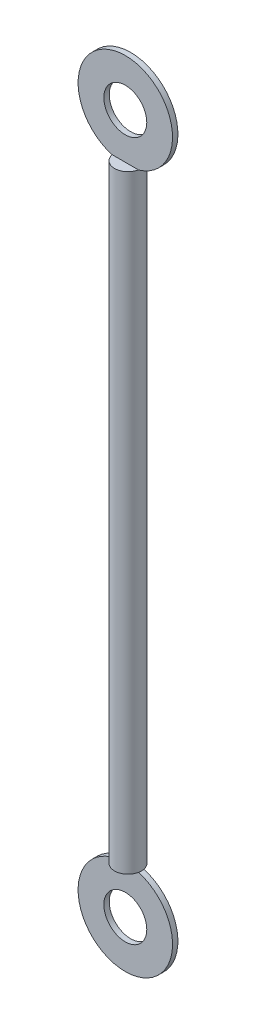
SolidWorks part; units mm, degrees
ref_plane "Front Plane" through (0, 0, 0) normal (0, 0, 1) x (1, 0, 0)
ref_plane "Top Plane" through (0, 0, 0) normal (0, 1, 0) x (1, 0, 0)
ref_plane "Right Plane" through (0, 0, 0) normal (1, 0, 0) x (0, 0, -1)
sketch "Sketch1" plane through (0, 0, 0) normal (0, 0, 1) x (1, 0, 0)
  line L0 (-7.9375, 26.7888) -> (7.9375, 26.7888) construction
  line L1 (0, 386.813) -> (0, 26.7888)
  line L2 (-7.9375, 26.7888) -> (7.9375, 26.7888)
  line L3 (-7.9375, 26.7888) -> (-7.9375, 386.813)
  line L4 (-7.9375, 386.813) -> (7.9375, 386.813)
  line L5 (7.9375, 26.7888) -> (7.9375, 386.813)
  line L6 (-7.9375, 206.8009) -> (7.9375, 206.8009) construction
  circle A0 centre (0, 0) radius 12.7
  arc A1 (-7.9375, 26.7888) -> (7.9375, 26.7888) centre (0, 0) ccw
  arc A2 (-7.9375, 386.813) -> (7.9375, 386.813) centre (0, 413.6018) cw
  circle A3 centre (0, 413.6018) radius 12.7
  dimension "D1" = 25.4
  dimension "D2" = 360.0242
  dimension "D4" = 27.94
  dimension "D3" = 15.875
revolve "Revolve1" add sketch "Sketch1" angle 360 about L1 region at (3.9688, 206.8009, 0)
extrude "Boss-Extrude1" add sketch "Sketch1<3>" along normal mid plane 3.175 contours L2 A1 A0 | L4 region at (-3.9687, 387.5951, 0) region at (3.9688, 26.0066, 0)
sketch "Sketch1<3>" plane through (0, 0, 0) normal (0, 0, 1) x (1, 0, 0) same geometry as "Sketch1"
scale "Scale1" scale about centroid uniform scaling yes scale factor 0.5
